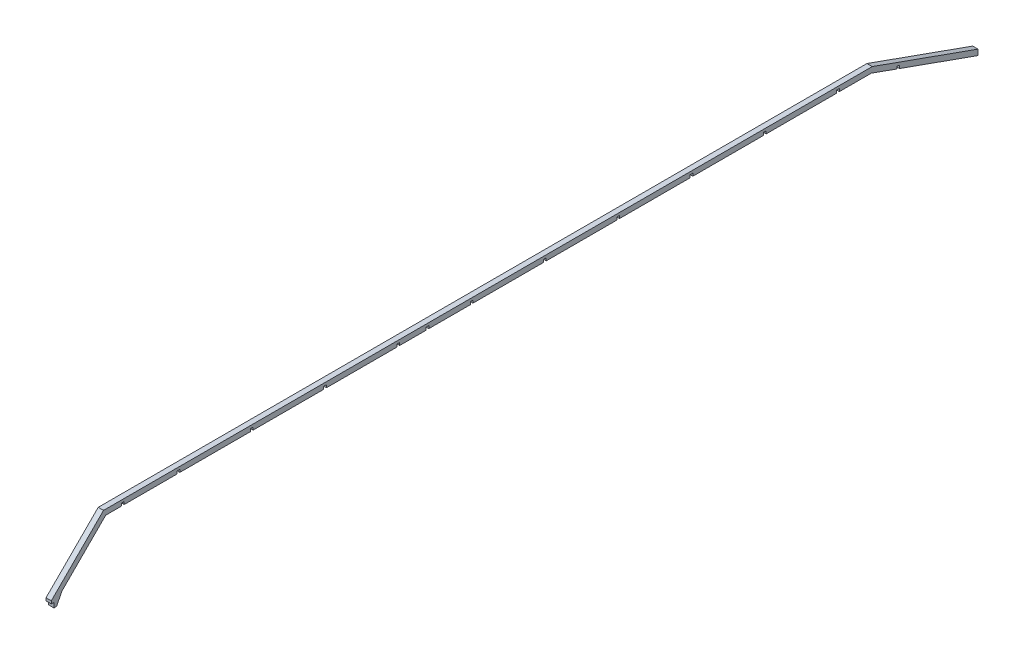
SolidWorks part; units mm, degrees
ref_plane "Спереди" through (0, 0, 0) normal (0, 0, 1) x (1, 0, 0)
ref_plane "Сверху" through (0, 0, 0) normal (0, 1, 0) x (1, 0, 0)
ref_plane "Справа" through (0, 0, 0) normal (1, 0, 0) x (0, 0, -1)
other "Configuration Table"
sketch "Эскиз1" plane through (0, 0, 0) normal (1, 0, 0) x (0, 0, -1)
  line L0 (-751.8866, -19.1422) -> (-733.9606, -19.1422)
  line L1 (115.1734, -19.1422) -> (144.0394, -29.4493)
  line L6 (160.4534, -35.3102) -> (162.4711, -29.6596) construction
  line L7 (-813.5251, -80.7807) -> (-751.8866, -19.1422) construction
  line L8 (-813.5251, -72.2954) -> (-813.5251, -80.7807) construction
  line L17 (147.0394, -30.5205) -> (147.0394, -27.5205)
  line L18 (147.0394, -27.5205) -> (144.0394, -26.4493)
  line L19 (144.0394, -26.4493) -> (144.0394, -29.4493)
  line L20 (147.0394, -30.5205) -> (236.0394, -62.2995)
  line L21 (79.0394, -19.1422) -> (79.0394, -16.1422)
  line L22 (79.0394, -16.1422) -> (76.0394, -16.1422)
  line L23 (76.0394, -16.1422) -> (76.0394, -19.1422)
  line L24 (79.0394, -19.1422) -> (115.1734, -19.1422)
  line L25 (-3.9606, -19.1422) -> (-3.9606, -16.1422)
  line L26 (-3.9606, -16.1422) -> (-6.9606, -16.1422)
  line L27 (-6.9606, -16.1422) -> (-6.9606, -19.1422)
  line L28 (-86.9606, -19.1422) -> (-86.9606, -16.1422)
  line L29 (-86.9606, -16.1422) -> (-89.9606, -16.1422)
  line L30 (-89.9606, -16.1422) -> (-89.9606, -19.1422)
  line L31 (-169.9606, -19.1422) -> (-169.9606, -16.1422)
  line L32 (-169.9606, -16.1422) -> (-172.9606, -16.1422)
  line L33 (-172.9606, -16.1422) -> (-172.9606, -19.1422)
  line L34 (-252.9606, -19.1422) -> (-252.9606, -16.1422)
  line L35 (-252.9606, -16.1422) -> (-255.9606, -16.1422)
  line L36 (-255.9606, -16.1422) -> (-255.9606, -19.1422)
  line L37 (-335.9606, -19.1422) -> (-335.9606, -16.1422)
  line L38 (-335.9606, -16.1422) -> (-338.9606, -16.1422)
  line L39 (-338.9606, -16.1422) -> (-338.9606, -19.1422)
  line L40 (-3.9606, -19.1422) -> (76.0394, -19.1422)
  line L41 (-86.9606, -19.1422) -> (-6.9606, -19.1422)
  line L42 (-169.9606, -19.1422) -> (-89.9606, -19.1422)
  line L43 (-252.9606, -19.1422) -> (-172.9606, -19.1422)
  line L44 (-335.9606, -19.1422) -> (-255.9606, -19.1422)
  line L45 (-385.9606, -19.1422) -> (-385.9606, -16.1422)
  line L46 (-385.9606, -16.1422) -> (-388.9606, -16.1422)
  line L47 (-388.9606, -16.1422) -> (-388.9606, -19.1422)
  line L48 (-385.9606, -19.1422) -> (-338.9606, -19.1422)
  line L49 (-418.9606, -19.1422) -> (-418.9606, -16.1422)
  line L50 (-418.9606, -16.1422) -> (-421.9606, -16.1422)
  line L51 (-421.9606, -16.1422) -> (-421.9606, -19.1422)
  line L52 (-418.9606, -19.1422) -> (-388.9606, -19.1422)
  line L53 (-501.9606, -19.1422) -> (-501.9606, -16.1422)
  line L54 (-501.9606, -16.1422) -> (-504.9606, -16.1422)
  line L55 (-504.9606, -16.1422) -> (-504.9606, -19.1422)
  line L56 (-584.9606, -19.1422) -> (-584.9606, -16.1422)
  line L57 (-584.9606, -16.1422) -> (-587.9606, -16.1422)
  line L58 (-587.9606, -16.1422) -> (-587.9606, -19.1422)
  line L59 (-667.9606, -19.1422) -> (-667.9606, -16.1422)
  line L60 (-667.9606, -16.1422) -> (-670.9606, -16.1422)
  line L61 (-670.9606, -16.1422) -> (-670.9606, -19.1422)
  line L62 (-501.9606, -19.1422) -> (-421.9606, -19.1422)
  line L63 (-584.9606, -19.1422) -> (-504.9606, -19.1422)
  line L64 (-667.9606, -19.1422) -> (-587.9606, -19.1422)
  line L65 (-730.9606, -19.1422) -> (-730.9606, -16.1422)
  line L66 (-730.9606, -16.1422) -> (-733.9606, -16.1422)
  line L67 (-733.9606, -16.1422) -> (-733.9606, -19.1422)
  line L68 (-730.9606, -19.1422) -> (-670.9606, -19.1422)
  line L69 (236.0394, -62.2995) -> (238.0571, -56.6489) construction
  line L70 (-3.9606, -19.1422) -> (-3.9606, -13.1422) construction
  line L71 (162.4711, -29.6596) -> (82.2261, -1.0067) construction
  line L72 (238.0571, -56.6489) -> (162.4711, -29.6596) construction
  line L73 (79.0394, -19.1422) -> (79.0394, -13.1422) construction
  line L74 (236.0394, -62.2995) -> (236.0394, -55.9285)
  line L75 (-3.9606, -13.1422) -> (116.2125, -13.1422) construction
  line L76 (-803.8198, -71.0753) -> (-808.0624, -66.8327) construction
  line L77 (-751.8866, -19.1422) -> (-756.1293, -14.8995) construction
  line L78 (-3.9606, -13.1422) -> (-770.7331, -13.1422) construction
  line L79 (-756.1293, -14.8995) -> (-813.5251, -72.2954) construction
  line L81 (-810.5251, -80.7807) -> (-807.5251, -80.7807)
  line L82 (-807.5251, -80.7807) -> (-801.5251, -80.7807) construction
  line L83 (-801.5251, -80.7807) -> (-801.5251, -68.7807) construction
  line L84 (-807.5251, -80.7807) -> (-801.5251, -68.7807)
  line L85 (-801.5251, -68.7807) -> (-751.8866, -19.1422)
  line L86 (-813.5251, -72.2954) -> (-754.3719, -13.1422)
  line L87 (-754.3719, -13.1422) -> (116.2125, -13.1422)
  line L88 (116.2125, -13.1422) -> (236.0394, -55.9285)
  line L89 (-813.5251, -72.2954) -> (-813.5251, -75.2954)
  line L90 (-813.5251, -75.2954) -> (-810.5251, -75.2954)
  line L91 (-810.5251, -75.2954) -> (-810.5251, -80.7807)
  point P49 (-388.9606, -17.6422)
  dimension "D1" = 160.35
  dimension "D2" = 128.34
  dimension "D4" = 6
  dimension "D5" = 6
  dimension "D6" = 867.06
  dimension "D7" = 6
  dimension "D8" = 3
  dimension "D9" = 3
  dimension "D10" = 6
  dimension "D11" = 81.17
  dimension "D12" = 3
  dimension "D13" = 65
  dimension "D14" = 3
  dimension "D15" = 3
  dimension "D16" = 3
  dimension "D17" = 80
  dimension "D18" = 3
  dimension "D19" = 80
  dimension "D20" = 3
  dimension "D21" = 80
  dimension "D22" = 3
  dimension "D23" = 80
  dimension "D24" = 3
  dimension "D25" = 80
  dimension "D26" = 3
  dimension "D27" = 47
  dimension "D28" = 3
  dimension "D29" = 3
  dimension "D30" = 30
  dimension "D31" = 3
  dimension "D32" = 80
  dimension "D33" = 3
  dimension "D34" = 80
  dimension "D35" = 80
  dimension "D36" = 3
  dimension "D37" = 3
  dimension "D38" = 60
  dimension "D39" = 6
  dimension "D40" = 6
extrude "Бобышка-Вытянуть3" add sketch "Эскиз1" along normal blind 6
